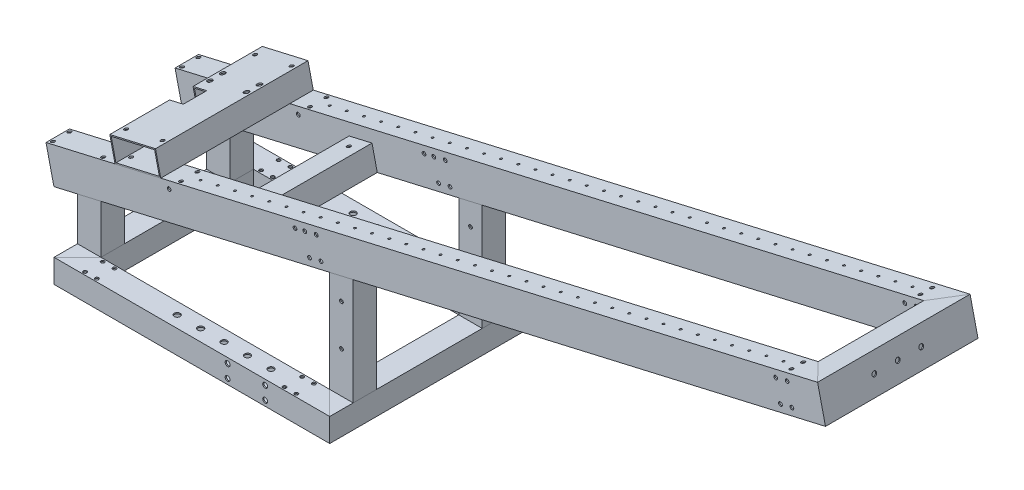
SolidWorks part; units mm, degrees
material "6061-T6 (SS)"
ref_plane "前视基准面" through (0, 0, 0) normal (0, 0, 1) x (1, 0, 0)
ref_plane "上视基准面" through (0, 0, 0) normal (0, 1, 0) x (1, 0, 0)
ref_plane "右视基准面" through (0, 0, 0) normal (1, 0, 0) x (0, 0, -1)
sketch3d "3D草图1"
  line L0 (0, 0, -212.485) -> (0, 0, 212.485) construction
  line L1 (0, 0, 75) -> (215, 0, 75)
  line L2 (215, 0, 75) -> (215, 0, -75)
  line L3 (215, 0, -75) -> (0, 0, -75)
  line L4 (0, 0, 0) -> (326.1616, 0, 0) construction
  line L5 (215, 0, 55) -> (215, 114.1, 55)
  line L6 (215, 0, -55) -> (215, 114.1, -55)
  line L7 (-33.4644, 56.7375, 55) -> (614.4917, 206.3299, 55)
  line L8 (-33.4644, 56.7375, -55) -> (614.4917, 206.3299, -55)
  line L9 (215, 114.1, 55) -> (395.6798, 114.1, 55) construction
  line L10 (0, 0, -75) -> (0, 0, 75)
  line L11 (0, 64.4633, 55) -> (0, 0, 55)
  line L12 (0, 0, 55) -> (215, 0, 55) construction
  line L13 (614.4917, 206.3299, -55) -> (614.4917, 206.3299, 55)
  line L14 (0, 0, -75) -> (0, 0, 55) construction
  line L15 (0, 64.4633, -55) -> (0, 0, -55)
  point P2 (0, 0, 0)
  point P10 (215, 0, 0)
  dimension "D3" = 55
  dimension "D1" = 215
  dimension "D2" = 150
  dimension "a" = 110
  dimension "D4" = 114.1
  dimension "D5" = 665
  dimension "h" = 255
  dimension "D8" = 13
  dimension "D6" = 255
other "方形管 20 X 20 X 2(1)"
ref_plane "基准面1" through (0, 0, -75) normal (0, 0, 1) x (1, 0, 0)
sketch "Sketch1" plane through (0, 0, -75) normal (0, 0, 1) x (1, 0, 0)
  line L0 (-9, 9) -> (-9, -9)
  line L1 (-10, 10) -> (10, 10)
  line L2 (-10, 10) -> (-10, -10)
  line L3 (-10, -10) -> (10, -10)
  line L4 (10, 10) -> (10, -10)
  line L5 (-10, 10) -> (10, -10) construction
  line L6 (-10, -10) -> (10, 10) construction
  line L7 (-9, -9) -> (9, -9)
  line L8 (9, 9) -> (9, -9)
  line L9 (-9, 9) -> (9, 9)
  point P0 (0, 0)
  dimension "D1" = 20
  dimension "D2" = 1
other "方形管 20 X 20 X 2(22)"
ref_plane "基准面3" through (-33.4644, 56.7375, 55) normal (0.9744, 0.225, 0) x (0.225, -0.9744, 0)
sketch "Sketch12" plane through (-33.4644, 56.7375, 55) normal (0.9744, 0.225, 0) x (0.225, -0.9744, 0)
  line L0 (-14, 9) -> (14, 9)
  line L1 (-15, 10) -> (15, 10)
  line L2 (-15, 10) -> (-15, -10)
  line L3 (-15, -10) -> (15, -10)
  line L4 (15, 10) -> (15, -10)
  line L5 (-15, 10) -> (15, -10) construction
  line L6 (-15, -10) -> (15, 10) construction
  line L7 (14, 9) -> (14, -9)
  line L8 (-14, -9) -> (14, -9)
  line L9 (-14, 9) -> (-14, -9)
  point P0 (0, 0)
  dimension "D1" = 20
  dimension "D2" = 30
  dimension "D3" = 1
other "剪裁/延伸4"
other "剪裁/延伸5"
sketch "草图4" plane through (638.3649, 147.3781, 0) normal (0.9744, 0.225, 0) x (0, 0, -1)
  line L0 (-65, 62.8111) -> (65, 62.8111) construction
  line L1 (-65, 77.8111) -> (-65, 47.8111) construction
  line L2 (65, 47.8111) -> (65, 77.8111) construction
  line L3 (0, 77.8111) -> (0, 47.8111) construction
  line L4 (65, 77.8111) -> (-65, 77.8111) construction
  line L5 (65, 47.8111) -> (-65, 47.8111) construction
  circle A0 centre (0, 62.8111) radius 2
  circle A1 centre (20, 62.8111) radius 2
  circle A2 centre (-20, 62.8111) radius 2
  dimension "D1" = 4
  dimension "D2" = 40
extrude "切除-拉伸1" cut sketch "草图4" against normal up to surface (20 mm away) up to face at (604.748, 204.0804, 0)
sketch "草图5" plane through (-17.5037, 75.8169, 0) normal (-0.225, 0.9744, 0) x (0.9744, 0.225, 0)
  line L0 (635.1565, -45) -> (-19.8435, -45) construction
  line L1 (-19.8435, 65) -> (655.1565, 65) construction
  line L2 (627.1565, 50) -> (627.1565, 60) construction
  line L3 (673.6837, 55) -> (-19.0857, 55) construction
  line L4 (655.1565, 65) -> (655.1565, -65) construction
  line L5 (615.1565, 55) -> (600.1565, 55) construction
  line L6 (27.1565, 48) -> (-16.8435, 48) construction
  line L7 (5.1565, 48) -> (5.1565, 75.8117) construction
  line L8 (-19.8435, 45) -> (-19.8435, 65) construction
  line L9 (0, 0) -> (900.0892, 0) construction
  line L10 (5.1565, -48) -> (5.1565, -75.8117) construction
  line L11 (27.1565, -48) -> (-16.8435, -48) construction
  line L12 (615.1565, -55) -> (600.1565, -55) construction
  line L13 (673.6837, -55) -> (-19.0857, -55) construction
  line L14 (-19.8435, 45) -> (635.1565, 45) construction
  line L15 (27.1565, 62) -> (-16.8435, 62) construction
  line L16 (-16.8435, 62) -> (-16.8435, 48) construction
  line L17 (27.1565, 62) -> (27.1565, 48) construction
  line L18 (27.1565, 55) -> (76.5565, 55) construction
  line L19 (95.1602, 62) -> (95.1602, 48) construction
  line L20 (95.1602, 55) -> (76.5565, 55) construction
  circle A1 centre (627.1565, 50) radius 1.6
  circle A3 centre (627.1565, 60) radius 1.6
  circle A6 centre (615.1565, 55) radius 1
  circle A7 centre (600.1565, 55) radius 1
  circle A8 centre (585.1565, 55) radius 1
  circle A9 centre (570.1565, 55) radius 1
  circle A10 centre (555.1565, 55) radius 1
  circle A11 centre (540.1565, 55) radius 1
  circle A12 centre (525.1565, 55) radius 1
  circle A13 centre (510.1565, 55) radius 1
  circle A14 centre (495.1565, 55) radius 1
  circle A15 centre (480.1565, 55) radius 1
  circle A16 centre (465.1565, 55) radius 1
  circle A17 centre (450.1565, 55) radius 1
  circle A18 centre (435.1565, 55) radius 1
  circle A19 centre (420.1565, 55) radius 1
  circle A20 centre (405.1565, 55) radius 1
  circle A21 centre (390.1565, 55) radius 1
  circle A22 centre (375.1565, 55) radius 1
  circle A23 centre (360.1565, 55) radius 1
  circle A24 centre (345.1565, 55) radius 1
  circle A25 centre (330.1565, 55) radius 1
  circle A26 centre (315.1565, 55) radius 1
  circle A27 centre (300.1565, 55) radius 1
  circle A28 centre (285.1565, 55) radius 1
  circle A29 centre (270.1565, 55) radius 1
  circle A30 centre (255.1565, 55) radius 1
  circle A31 centre (240.1565, 55) radius 1
  circle A32 centre (225.1565, 55) radius 1
  circle A33 centre (210.1565, 55) radius 1
  circle A34 centre (195.1565, 55) radius 1
  circle A35 centre (180.1565, 55) radius 1
  circle A36 centre (165.1565, 55) radius 1
  circle A37 centre (150.1565, 55) radius 1
  circle A38 centre (135.1565, 55) radius 1
  circle A39 centre (120.1565, 55) radius 1
  circle A40 centre (105.1565, 55) radius 1
  circle A44 centre (-16.8435, 48) radius 1.6
  circle A45 centre (27.1565, 48) radius 1.6
  circle A46 centre (44.5565, 55) radius 1.6
  circle A47 centre (76.5565, 55) radius 1.6
  circle A48 centre (95.1602, 48) radius 1.6
  circle A49 centre (-16.8435, 62) radius 1.6
  circle A50 centre (27.1565, 62) radius 1.6
  circle A51 centre (95.1602, 62) radius 1.6
  circle A52 centre (95.1602, -62) radius 1.6
  circle A53 centre (27.1565, -62) radius 1.6
  circle A54 centre (-16.8435, -62) radius 1.6
  circle A55 centre (95.1602, -48) radius 1.6
  circle A56 centre (76.5565, -55) radius 1.6
  circle A57 centre (44.5565, -55) radius 1.6
  circle A58 centre (27.1565, -48) radius 1.6
  circle A59 centre (-16.8435, -48) radius 1.6
  circle A63 centre (105.1565, -55) radius 1
  circle A64 centre (120.1565, -55) radius 1
  circle A65 centre (135.1565, -55) radius 1
  circle A66 centre (150.1565, -55) radius 1
  circle A67 centre (165.1565, -55) radius 1
  circle A68 centre (180.1565, -55) radius 1
  circle A69 centre (195.1565, -55) radius 1
  circle A70 centre (210.1565, -55) radius 1
  circle A71 centre (225.1565, -55) radius 1
  circle A72 centre (240.1565, -55) radius 1
  circle A73 centre (255.1565, -55) radius 1
  circle A74 centre (270.1565, -55) radius 1
  circle A75 centre (285.1565, -55) radius 1
  circle A76 centre (300.1565, -55) radius 1
  circle A77 centre (315.1565, -55) radius 1
  circle A78 centre (330.1565, -55) radius 1
  circle A79 centre (345.1565, -55) radius 1
  circle A80 centre (360.1565, -55) radius 1
  circle A81 centre (375.1565, -55) radius 1
  circle A82 centre (390.1565, -55) radius 1
  circle A83 centre (405.1565, -55) radius 1
  circle A84 centre (420.1565, -55) radius 1
  circle A85 centre (435.1565, -55) radius 1
  circle A86 centre (450.1565, -55) radius 1
  circle A87 centre (465.1565, -55) radius 1
  circle A88 centre (480.1565, -55) radius 1
  circle A89 centre (495.1565, -55) radius 1
  circle A90 centre (510.1565, -55) radius 1
  circle A91 centre (525.1565, -55) radius 1
  circle A92 centre (540.1565, -55) radius 1
  circle A93 centre (555.1565, -55) radius 1
  circle A94 centre (570.1565, -55) radius 1
  circle A95 centre (585.1565, -55) radius 1
  circle A96 centre (600.1565, -55) radius 1
  circle A97 centre (615.1565, -55) radius 1
  circle A100 centre (627.1565, -60) radius 1.6
  circle A102 centre (627.1565, -50) radius 1.6
  dimension "D6" = 2
  dimension "D10" = 3.2
  dimension "D3" = 3.2
  dimension "D18" = 5
  dimension "D13" = 3
  dimension "D19" = 14
  dimension "D2" = 10
  dimension "D4" = 28
  dimension "D5" = 10
  dimension "D7" = 40
  dimension "D9" = 15
  dimension "D11" = 25
  dimension "D12" = 44
  dimension "D14" = 14
  dimension "D15" = 64.4
  dimension "D16" = 32
  dimension "D17" = 532
  dimension "D8" = 35
extrude "切除-拉伸2" cut sketch "草图5" against normal up to surface (30 mm away) up to face at (293.8879, 116.9182, 55)
sketch "草图6" plane through (0, -10, 0) normal (0, -1, 0) x (1, 0, 0)
  line L0 (215, -75) -> (-27.0057, -75) construction
  line L1 (205, -65) -> (225, -85) construction
  line L3 (228.748, 0) -> (-86.5381, 0) construction
  line L4 (24, -67.5) -> (194, -67.5) construction
  line L5 (24, 67.5) -> (194, 67.5) construction
  line L6 (225, -85) -> (225, 85) construction
  circle A0 centre (24, -82.5) radius 1.5
  circle A1 centre (14, -82.5) radius 1.5
  circle A2 centre (14, -67.5) radius 1.5
  circle A3 centre (24, -67.5) radius 1.5
  circle A4 centre (194, -67.5) radius 1.5
  circle A5 centre (194, -82.5) radius 1.5
  circle A6 centre (184, -82.5) radius 1.5
  circle A7 centre (184, -67.5) radius 1.5
  circle A8 centre (184, 67.5) radius 1.5
  circle A9 centre (184, 82.5) radius 1.5
  circle A10 centre (194, 82.5) radius 1.5
  circle A11 centre (194, 67.5) radius 1.5
  circle A12 centre (24, 67.5) radius 1.5
  circle A13 centre (14, 67.5) radius 1.5
  circle A14 centre (14, 82.5) radius 1.5
  circle A15 centre (24, 82.5) radius 1.5
  dimension "D1" = 3
  dimension "D2" = 15
  dimension "D3" = 31
  dimension "D4" = 10
  dimension "D5" = 2
  dimension "D6" = 170
extrude "切除-拉伸3" cut sketch "草图6" against normal up to surface (20 mm away)
sketch "草图9" plane through (0, 0, -45) normal (0, 0, 1) x (1, 0, 0)
  line L0 (111.5664, 95.352) -> (131.0538, 99.851)
  line L1 (111.5664, 95.352) -> (116.0654, 75.8646)
  line L2 (131.0538, 99.851) -> (135.5528, 80.3636)
  line L3 (116.0654, 75.8646) -> (135.5528, 80.3636)
  line L4 (111.5664, 95.352) -> (135.5528, 80.3636) construction
  line L5 (131.0538, 99.851) -> (116.0654, 75.8646) construction
  line L6 (-30.0901, 42.1219) -> (608.1223, 189.4649) construction
  line L7 (112.7657, 94.6026) -> (130.3044, 98.6517)
  line L8 (130.3044, 98.6517) -> (134.3535, 81.113)
  line L9 (116.8148, 77.0639) -> (134.3535, 81.113)
  line L10 (112.7657, 94.6026) -> (116.8148, 77.0639)
  line L11 (-30.0901, 42.1219) -> (-36.8386, 71.353) construction
  point P1 (123.5596, 87.8578)
  dimension "D1" = 20
  dimension "D2" = 1
  dimension "D3" = 170
extrude "凸台-拉伸1" add sketch "草图9" along normal up to next (90 mm away) separate body
sketch "草图13" plane through (-17.5037, 75.8169, 0) normal (-0.225, 0.9744, 0) x (0.9744, 0.225, 0)
  line L0 (0.1565, -42) -> (20.1565, -42)
  line L1 (643.8428, 65) -> (-19.8435, 65)
  line L2 (673.2102, 71.74) -> (673.2102, -71.74)
  line L3 (643.8428, -65) -> (-19.8435, -65)
  line L4 (-19.8435, 65) -> (-19.8435, -65)
  line L6 (649.4996, 70.6569) -> (629.4996, 50.6569)
  line L7 (643.8428, 65) -> (651.6297, 72.7869)
  line L8 (660.8133, 59.3431) -> (640.8133, 39.3431)
  line L9 (673.2102, 71.74) -> (662.9434, 61.4732)
  line L10 (-19.8435, 45) -> (635.1565, 45) construction
  line L11 (655.1565, 65) -> (635.1565, 45) construction
  line L16 (635.1565, 0) -> (0, 0) construction
  line L17 (635.1565, 45) -> (635.1565, -45) construction
  line L20 (643.8428, -65) -> (651.6297, -72.7869)
  line L21 (673.2102, -71.74) -> (662.9434, -61.4732)
  line L22 (127.1565, 10) -> (127.1565, -10)
  line L23 (127.1565, 35) -> (130.1565, 35)
  line L24 (127.1565, 35) -> (127.1565, 15)
  line L25 (127.1565, 15) -> (130.1565, 15)
  line L26 (150.1565, -45) -> (150.1565, 45)
  line L27 (130.1565, -45) -> (150.1565, -45)
  line L28 (130.1565, 45) -> (130.1565, -45)
  line L29 (150.1565, 45) -> (130.1565, 45)
  line L30 (150.1565, -45) -> (150.1565, 45) construction
  line L32 (130.1565, 45) -> (130.1565, -45) construction
  line L34 (130.1565, 35) -> (130.1565, 15)
  line L35 (127.1565, 10) -> (130.1565, 10)
  line L36 (130.1565, 10) -> (130.1565, -10)
  line L37 (127.1565, -10) -> (130.1565, -10)
  line L38 (127.1565, -15) -> (127.1565, -35)
  line L39 (127.1565, -15) -> (130.1565, -15)
  line L40 (130.1565, -15) -> (130.1565, -35)
  line L41 (127.1565, -35) -> (130.1565, -35)
  line L42 (635.1565, -45) -> (-19.8435, -45) construction
  line L43 (140.1565, 45) -> (140.1565, -45) construction
  line L44 (150.1565, 45) -> (130.1565, 45) construction
  line L45 (150.1565, -45) -> (130.1565, -45) construction
  line L46 (153.1565, -15) -> (150.1565, -15)
  line L47 (150.1565, -15) -> (150.1565, -35)
  line L48 (153.1565, -35) -> (150.1565, -35)
  line L49 (153.1565, -15) -> (153.1565, -35)
  line L50 (153.1565, 10) -> (150.1565, 10)
  line L51 (150.1565, 10) -> (150.1565, -10)
  line L52 (153.1565, -10) -> (150.1565, -10)
  line L53 (153.1565, 10) -> (153.1565, -10)
  line L54 (153.1565, 15) -> (150.1565, 15)
  line L55 (150.1565, 35) -> (150.1565, 15)
  line L56 (153.1565, 35) -> (150.1565, 35)
  line L57 (153.1565, 35) -> (153.1565, 15)
  line L58 (632.1565, 10) -> (632.1565, -10)
  line L59 (632.1565, 35) -> (635.1565, 35)
  line L60 (632.1565, 35) -> (632.1565, 15)
  line L61 (632.1565, 15) -> (635.1565, 15)
  line L62 (635.1565, 35) -> (635.1565, 15)
  line L63 (632.1565, 10) -> (635.1565, 10)
  line L64 (635.1565, 10) -> (635.1565, -10)
  line L65 (632.1565, -10) -> (635.1565, -10)
  line L66 (632.1565, -15) -> (632.1565, -35)
  line L67 (632.1565, -15) -> (635.1565, -15)
  line L68 (635.1565, -15) -> (635.1565, -35)
  line L69 (632.1565, -35) -> (635.1565, -35)
  line L70 (130.1565, 37) -> (150.1565, 37)
  line L71 (130.1565, 53) -> (150.1565, 53)
  line L72 (130.1565, -53) -> (150.1565, -53)
  line L73 (130.1565, -37) -> (150.1565, -37)
  line L74 (0.1565, 47.5916) -> (130.1565, 47.5916) construction
  line L75 (-19.8435, 45) -> (0.1565, 45) construction
  line L76 (-19.8435, 45) -> (-19.8435, -45) construction
  line L77 (-19.8435, -45) -> (0.1565, -45) construction
  line L78 (0.1565, 45) -> (0.1565, -45) construction
  line L79 (65.1565, 47.5916) -> (65.1565, 105.8655) construction
  line L80 (3.1565, -15) -> (0.1565, -15)
  line L81 (0.1565, -15) -> (0.1565, -35)
  line L82 (3.1565, -35) -> (0.1565, -35)
  line L83 (3.1565, -15) -> (3.1565, -35)
  line L84 (3.1565, 10) -> (0.1565, 10)
  line L85 (0.1565, 10) -> (0.1565, -10)
  line L86 (3.1565, -10) -> (0.1565, -10)
  line L87 (3.1565, 10) -> (3.1565, -10)
  line L88 (3.1565, 15) -> (0.1565, 15)
  line L89 (0.1565, 35) -> (0.1565, 15)
  line L90 (3.1565, 35) -> (0.1565, 35)
  line L91 (3.1565, 35) -> (3.1565, 15)
  line L92 (20.1565, -45) -> (20.1565, -42)
  line L93 (0.1565, 45) -> (20.1565, 45)
  line L94 (0.1565, 45) -> (0.1565, 42)
  line L95 (0.1565, 42) -> (20.1565, 42)
  line L96 (20.1565, 45) -> (20.1565, 42)
  line L97 (0.1565, -45) -> (20.1565, -45)
  line L98 (0.1565, -45) -> (0.1565, -42)
  line L99 (66.2676, 45) -> (66.2676, 42)
  line L100 (66.2676, 45) -> (86.2676, 45)
  line L101 (86.2676, 45) -> (86.2676, 42)
  line L102 (66.2676, 42) -> (86.2676, 42)
  line L103 (66.2676, -42) -> (86.2676, -42)
  line L104 (86.2676, -45) -> (86.2676, -42)
  line L105 (66.2676, -45) -> (86.2676, -45)
  line L106 (66.2676, -45) -> (66.2676, -42)
  line L115 (198.4898, 45) -> (198.4898, 42)
  line L116 (198.4898, 45) -> (218.4898, 45)
  line L117 (218.4898, 45) -> (218.4898, 42)
  line L118 (198.4898, 42) -> (218.4898, 42)
  line L119 (198.4898, -42) -> (218.4898, -42)
  line L120 (218.4898, -45) -> (218.4898, -42)
  line L121 (198.4898, -45) -> (218.4898, -45)
  line L122 (198.4898, -45) -> (198.4898, -42)
  line L123 (264.6009, 45) -> (264.6009, 42)
  line L124 (264.6009, 45) -> (284.6009, 45)
  line L125 (284.6009, 45) -> (284.6009, 42)
  line L126 (264.6009, 42) -> (284.6009, 42)
  line L127 (264.6009, -42) -> (284.6009, -42)
  line L128 (284.6009, -45) -> (284.6009, -42)
  line L129 (264.6009, -45) -> (284.6009, -45)
  line L130 (264.6009, -45) -> (264.6009, -42)
  line L131 (330.712, 45) -> (330.712, 42)
  line L132 (330.712, 45) -> (350.712, 45)
  line L133 (350.712, 45) -> (350.712, 42)
  line L134 (330.712, 42) -> (350.712, 42)
  line L135 (330.712, -42) -> (350.712, -42)
  line L136 (350.712, -45) -> (350.712, -42)
  line L137 (330.712, -45) -> (350.712, -45)
  line L138 (330.712, -45) -> (330.712, -42)
  line L139 (396.8231, 45) -> (396.8231, 42)
  line L140 (396.8231, 45) -> (416.8231, 45)
  line L141 (416.8231, 45) -> (416.8231, 42)
  line L142 (396.8231, 42) -> (416.8231, 42)
  line L143 (396.8231, -42) -> (416.8231, -42)
  line L144 (416.8231, -45) -> (416.8231, -42)
  line L145 (396.8231, -45) -> (416.8231, -45)
  line L146 (396.8231, -45) -> (396.8231, -42)
  line L147 (462.9343, 45) -> (462.9343, 42)
  line L148 (462.9343, 45) -> (482.9343, 45)
  line L149 (482.9343, 45) -> (482.9343, 42)
  line L150 (462.9343, 42) -> (482.9343, 42)
  line L151 (462.9343, -42) -> (482.9343, -42)
  line L152 (482.9343, -45) -> (482.9343, -42)
  line L153 (462.9343, -45) -> (482.9343, -45)
  line L154 (462.9343, -45) -> (462.9343, -42)
  line L155 (529.0454, 45) -> (529.0454, 42)
  line L156 (529.0454, 45) -> (549.0454, 45)
  line L157 (549.0454, 45) -> (549.0454, 42)
  line L158 (529.0454, 42) -> (549.0454, 42)
  line L159 (529.0454, -42) -> (549.0454, -42)
  line L160 (549.0454, -45) -> (549.0454, -42)
  line L161 (529.0454, -45) -> (549.0454, -45)
  line L162 (529.0454, -45) -> (529.0454, -42)
  line L163 (595.1565, 45) -> (595.1565, 42)
  line L164 (595.1565, 45) -> (615.1565, 45)
  line L165 (615.1565, 45) -> (615.1565, 42)
  line L166 (595.1565, 42) -> (615.1565, 42)
  line L167 (595.1565, -42) -> (615.1565, -42)
  line L168 (615.1565, -45) -> (615.1565, -42)
  line L169 (595.1565, -45) -> (615.1565, -45)
  line L170 (595.1565, -45) -> (595.1565, -42)
  line L171 (132.3787, 45) -> (132.3787, 42) [skipped]
  line L172 (132.3787, 42) -> (152.3787, 42) [skipped]
  line L173 (152.3787, 45) -> (152.3787, 42) [skipped]
  line L174 (132.3787, 45) -> (152.3787, 45) [skipped]
  line L175 (132.3787, -42) -> (152.3787, -42) [skipped]
  line L176 (152.3787, -45) -> (152.3787, -42) [skipped]
  line L177 (132.3787, -45) -> (152.3787, -45) [skipped]
  line L178 (132.3787, -45) -> (132.3787, -42) [skipped]
  line L179 (651.6297, 72.7869) -> (656.4558, 45)
  line L180 (635.1565, 45) -> (655.1565, 65) construction
  line L181 (662.9434, 61.4732) -> (635.1565, 66.2993)
  line L182 (656.4558, 45) -> (635.1565, 66.2993)
  line L183 (662.9434, -61.4732) -> (635.1565, -66.2993)
  line L184 (656.4558, -45) -> (635.1565, -66.2993)
  line L185 (651.6297, -72.7869) -> (656.4558, -45)
  arc A2 (130.1565, 53) -> (130.1565, 37) centre (130.1565, 45) ccw
  circle A3 centre (95.1602, 62) radius 1.6
  circle A4 centre (95.1602, 62) radius 1.6
  circle A5 centre (27.1565, 62) radius 1.6
  circle A6 centre (27.1565, 62) radius 1.6
  circle A7 centre (-16.8435, 62) radius 1.6
  circle A8 centre (-16.8435, 62) radius 1.6
  circle A9 centre (95.1602, 48) radius 1.6
  circle A10 centre (95.1602, 48) radius 1.6
  circle A11 centre (76.5565, 55) radius 1.6
  circle A12 centre (76.5565, 55) radius 1.6
  circle A13 centre (44.5565, 55) radius 1.6
  circle A14 centre (44.5565, 55) radius 1.6
  circle A15 centre (27.1565, 48) radius 1.6
  circle A16 centre (27.1565, 48) radius 1.6
  circle A17 centre (-16.8435, 48) radius 1.6
  circle A18 centre (-16.8435, 48) radius 1.6
  circle A19 centre (105.1565, 55) radius 1
  circle A20 centre (105.1565, 55) radius 1
  circle A21 centre (120.1565, 55) radius 1
  circle A22 centre (120.1565, 55) radius 1
  circle A23 centre (135.1565, 55) radius 1
  circle A24 centre (135.1565, 55) radius 1
  circle A25 centre (150.1565, 55) radius 1
  circle A26 centre (150.1565, 55) radius 1
  circle A27 centre (165.1565, 55) radius 1
  circle A28 centre (165.1565, 55) radius 1
  circle A29 centre (180.1565, 55) radius 1
  circle A30 centre (180.1565, 55) radius 1
  circle A31 centre (195.1565, 55) radius 1
  circle A32 centre (195.1565, 55) radius 1
  circle A33 centre (210.1565, 55) radius 1
  circle A34 centre (210.1565, 55) radius 1
  circle A35 centre (225.1565, 55) radius 1
  circle A36 centre (225.1565, 55) radius 1
  circle A37 centre (240.1565, 55) radius 1
  circle A38 centre (240.1565, 55) radius 1
  circle A39 centre (255.1565, 55) radius 1
  circle A40 centre (255.1565, 55) radius 1
  circle A41 centre (270.1565, 55) radius 1
  circle A42 centre (270.1565, 55) radius 1
  circle A43 centre (285.1565, 55) radius 1
  circle A44 centre (285.1565, 55) radius 1
  circle A45 centre (300.1565, 55) radius 1
  circle A46 centre (300.1565, 55) radius 1
  circle A47 centre (315.1565, 55) radius 1
  circle A48 centre (315.1565, 55) radius 1
  circle A49 centre (330.1565, 55) radius 1
  circle A50 centre (330.1565, 55) radius 1
  circle A51 centre (345.1565, 55) radius 1
  circle A52 centre (345.1565, 55) radius 1
  circle A53 centre (360.1565, 55) radius 1
  circle A54 centre (360.1565, 55) radius 1
  circle A55 centre (375.1565, 55) radius 1
  circle A56 centre (375.1565, 55) radius 1
  circle A57 centre (390.1565, 55) radius 1
  circle A58 centre (390.1565, 55) radius 1
  circle A59 centre (405.1565, 55) radius 1
  circle A60 centre (405.1565, 55) radius 1
  circle A61 centre (420.1565, 55) radius 1
  circle A62 centre (420.1565, 55) radius 1
  circle A63 centre (435.1565, 55) radius 1
  circle A64 centre (435.1565, 55) radius 1
  circle A65 centre (450.1565, 55) radius 1
  circle A66 centre (450.1565, 55) radius 1
  circle A67 centre (465.1565, 55) radius 1
  circle A68 centre (465.1565, 55) radius 1
  circle A69 centre (480.1565, 55) radius 1
  circle A70 centre (480.1565, 55) radius 1
  circle A71 centre (495.1565, 55) radius 1
  circle A72 centre (495.1565, 55) radius 1
  circle A73 centre (510.1565, 55) radius 1
  circle A74 centre (510.1565, 55) radius 1
  circle A75 centre (525.1565, 55) radius 1
  circle A76 centre (525.1565, 55) radius 1
  circle A77 centre (540.1565, 55) radius 1
  circle A78 centre (540.1565, 55) radius 1
  circle A79 centre (555.1565, 55) radius 1
  circle A80 centre (555.1565, 55) radius 1
  circle A81 centre (570.1565, 55) radius 1
  circle A82 centre (570.1565, 55) radius 1
  circle A83 centre (585.1565, 55) radius 1
  circle A84 centre (585.1565, 55) radius 1
  circle A85 centre (600.1565, 55) radius 1
  circle A86 centre (600.1565, 55) radius 1
  circle A87 centre (615.1565, 55) radius 1
  circle A88 centre (615.1565, 55) radius 1
  circle A89 centre (627.1565, 60) radius 1.6
  circle A90 centre (627.1565, 60) radius 1.6
  circle A91 centre (627.1565, 50) radius 1.6
  circle A92 centre (627.1565, 50) radius 1.6
  circle A93 centre (627.1565, -50) radius 1.6
  circle A94 centre (627.1565, -50) radius 1.6
  circle A95 centre (627.1565, -60) radius 1.6
  circle A96 centre (627.1565, -60) radius 1.6
  circle A97 centre (615.1565, -55) radius 1
  circle A98 centre (615.1565, -55) radius 1
  circle A99 centre (600.1565, -55) radius 1
  circle A100 centre (600.1565, -55) radius 1
  circle A101 centre (585.1565, -55) radius 1
  circle A102 centre (585.1565, -55) radius 1
  circle A103 centre (570.1565, -55) radius 1
  circle A104 centre (570.1565, -55) radius 1
  circle A105 centre (555.1565, -55) radius 1
  circle A106 centre (555.1565, -55) radius 1
  circle A107 centre (540.1565, -55) radius 1
  circle A108 centre (540.1565, -55) radius 1
  circle A109 centre (525.1565, -55) radius 1
  circle A110 centre (525.1565, -55) radius 1
  circle A111 centre (510.1565, -55) radius 1
  circle A112 centre (510.1565, -55) radius 1
  circle A113 centre (495.1565, -55) radius 1
  circle A114 centre (495.1565, -55) radius 1
  circle A115 centre (480.1565, -55) radius 1
  circle A116 centre (480.1565, -55) radius 1
  circle A117 centre (465.1565, -55) radius 1
  circle A118 centre (465.1565, -55) radius 1
  circle A119 centre (450.1565, -55) radius 1
  circle A120 centre (450.1565, -55) radius 1
  circle A121 centre (435.1565, -55) radius 1
  circle A122 centre (435.1565, -55) radius 1
  circle A123 centre (420.1565, -55) radius 1
  circle A124 centre (420.1565, -55) radius 1
  circle A125 centre (405.1565, -55) radius 1
  circle A126 centre (405.1565, -55) radius 1
  circle A127 centre (390.1565, -55) radius 1
  circle A128 centre (390.1565, -55) radius 1
  circle A129 centre (375.1565, -55) radius 1
  circle A130 centre (375.1565, -55) radius 1
  circle A131 centre (360.1565, -55) radius 1
  circle A132 centre (360.1565, -55) radius 1
  circle A133 centre (345.1565, -55) radius 1
  circle A134 centre (345.1565, -55) radius 1
  circle A135 centre (330.1565, -55) radius 1
  circle A136 centre (330.1565, -55) radius 1
  circle A137 centre (315.1565, -55) radius 1
  circle A138 centre (315.1565, -55) radius 1
  circle A139 centre (300.1565, -55) radius 1
  circle A140 centre (300.1565, -55) radius 1
  circle A141 centre (285.1565, -55) radius 1
  circle A142 centre (285.1565, -55) radius 1
  circle A143 centre (270.1565, -55) radius 1
  circle A144 centre (270.1565, -55) radius 1
  circle A145 centre (255.1565, -55) radius 1
  circle A146 centre (255.1565, -55) radius 1
  circle A147 centre (240.1565, -55) radius 1
  circle A148 centre (240.1565, -55) radius 1
  circle A149 centre (225.1565, -55) radius 1
  circle A150 centre (225.1565, -55) radius 1
  circle A151 centre (210.1565, -55) radius 1
  circle A152 centre (210.1565, -55) radius 1
  circle A153 centre (195.1565, -55) radius 1
  circle A154 centre (195.1565, -55) radius 1
  circle A155 centre (180.1565, -55) radius 1
  circle A156 centre (180.1565, -55) radius 1
  circle A157 centre (165.1565, -55) radius 1
  circle A158 centre (165.1565, -55) radius 1
  circle A159 centre (150.1565, -55) radius 1
  circle A160 centre (150.1565, -55) radius 1
  circle A161 centre (135.1565, -55) radius 1
  circle A162 centre (135.1565, -55) radius 1
  circle A163 centre (120.1565, -55) radius 1
  circle A164 centre (120.1565, -55) radius 1
  circle A165 centre (105.1565, -55) radius 1
  circle A166 centre (105.1565, -55) radius 1
  circle A167 centre (-16.8435, -48) radius 1.6
  circle A168 centre (-16.8435, -48) radius 1.6
  circle A169 centre (27.1565, -48) radius 1.6
  circle A170 centre (27.1565, -48) radius 1.6
  circle A171 centre (44.5565, -55) radius 1.6
  circle A172 centre (44.5565, -55) radius 1.6
  circle A173 centre (76.5565, -55) radius 1.6
  circle A174 centre (76.5565, -55) radius 1.6
  circle A175 centre (95.1602, -48) radius 1.6
  circle A176 centre (95.1602, -48) radius 1.6
  circle A177 centre (-16.8435, -62) radius 1.6
  circle A178 centre (-16.8435, -62) radius 1.6
  circle A179 centre (27.1565, -62) radius 1.6
  circle A180 centre (27.1565, -62) radius 1.6
  circle A181 centre (95.1602, -62) radius 1.6
  circle A182 centre (95.1602, -62) radius 1.6
  arc A183 (150.1565, 37) -> (150.1565, 53) centre (150.1565, 45) ccw
  arc A184 (150.1565, -37) -> (150.1565, -53) centre (150.1565, -45) cw
  arc A185 (130.1565, -53) -> (130.1565, -37) centre (130.1565, -45) cw
  dimension "D104" = 16
  dimension "D94" = 3
  dimension "D95" = 20
  dimension "D97" = 10
  dimension "D98" = 10
  dimension "D99" = 20
  dimension "D100" = 10
  dimension "D101" = 3
  dimension "D103" = 10
  dimension "D105" = 10
  dimension "D106" = 3
  dimension "D107" = 20
  dimension "D108" = 20
  dimension "D109" = 20
  dimension "D1" = 8
  dimension "D2" = 8
  dimension "D3" = 0
  dimension "D4" = 0
  dimension "D5" = 0
  dimension "D6" = 0
  dimension "D7" = 0
  dimension "D8" = 0
  dimension "D9" = 0
  dimension "D10" = 0
  dimension "D11" = 0
  dimension "D12" = 0
  dimension "D13" = 0
  dimension "D14" = 0
  dimension "D15" = 0
  dimension "D16" = 0
  dimension "D17" = 0
  dimension "D18" = 0
  dimension "D19" = 0
  dimension "D20" = 0
  dimension "D21" = 0
  dimension "D22" = 0
  dimension "D23" = 0
  dimension "D24" = 0
  dimension "D25" = 0
  dimension "D26" = 0
  dimension "D27" = 0
  dimension "D28" = 0
  dimension "D29" = 0
  dimension "D30" = 0
  dimension "D31" = 0
  dimension "D32" = 0
  dimension "D33" = 0
  dimension "D34" = 0
  dimension "D35" = 0
  dimension "D36" = 0
  dimension "D37" = 0
  dimension "D38" = 0
  dimension "D39" = 0
  dimension "D40" = 0
  dimension "D41" = 0
  dimension "D42" = 0
  dimension "D43" = 0
  dimension "D44" = 0
  dimension "D45" = 0
  dimension "D46" = 0
  dimension "D47" = 0
  dimension "D48" = 0
  dimension "D49" = 0
  dimension "D50" = 0
  dimension "D51" = 0
  dimension "D52" = 0
  dimension "D53" = 0
  dimension "D54" = 0
  dimension "D55" = 0
  dimension "D56" = 0
  dimension "D57" = 0
  dimension "D58" = 0
  dimension "D59" = 0
  dimension "D60" = 0
  dimension "D61" = 0
  dimension "D62" = 0
  dimension "D63" = 0
  dimension "D64" = 0
  dimension "D65" = 0
  dimension "D66" = 0
  dimension "D67" = 0
  dimension "D68" = 0
  dimension "D69" = 0
  dimension "D70" = 0
  dimension "D71" = 0
  dimension "D72" = 0
  dimension "D73" = 0
  dimension "D74" = 0
  dimension "D75" = 0
  dimension "D76" = 0
  dimension "D77" = 0
  dimension "D78" = 0
  dimension "D79" = 0
  dimension "D80" = 0
  dimension "D81" = 0
  dimension "D82" = 0
  dimension "D83" = 0
  dimension "D84" = 0
  dimension "D85" = 0
  dimension "D86" = 0
  dimension "D87" = 0
  dimension "D88" = 0
  dimension "D89" = 0
  dimension "D90" = 0
  dimension "D91" = 0
  dimension "D92" = 0
  dimension "D93" = 0
  dimension "D96" = 3
  dimension "D102" = 3
extrude "凸台-拉伸2" [suppressed] add sketch "草图13" along normal blind 2 separate body
sketch "草图15" plane through (0, 0, 65) normal (0, 0, 1) x (1, 0, 0)
  line L0 (624.2354, 208.5794) -> (596.9531, 202.2808) construction
  line L1 (627.6097, 193.9639) -> (620.8612, 223.195) construction
  line L2 (620.8612, 223.195) -> (-36.8386, 71.353) construction
  line L3 (596.9531, 202.2808) -> (593.5788, 216.8964) construction
  line L4 (596.9531, 202.2808) -> (592.0812, 201.1561) construction
  line L5 (592.0812, 201.1561) -> (588.7069, 215.7716) construction
  line L6 (-33.4644, 56.7375) -> (297.7909, 133.2138) construction
  line L7 (-36.8386, 71.353) -> (-30.0901, 42.1219) construction
  line L8 (183.7443, 116.1208) -> (193.488, 118.3703) construction
  line L9 (183.7443, 116.1208) -> (187.7935, 98.5821) construction
  circle A0 centre (594.9285, 211.0501) radius 1.6
  circle A1 centre (598.9776, 193.5115) radius 1.6
  circle A2 centre (589.2339, 191.262) radius 1.6
  circle A3 centre (585.1848, 208.8006) radius 1.6
  circle A8 centre (183.7443, 116.1208) radius 1.6
  circle A9 centre (193.488, 118.3703) radius 1.6
  circle A10 centre (197.5372, 100.8316) radius 1.6
  circle A11 centre (187.7935, 98.5821) radius 1.6
  dimension "D2" = 3.2
  dimension "D3" = 18
  dimension "D6" = 18
  dimension "D5" = 10
  dimension "D7" = 225
  dimension "D8" = 3.2
  dimension "D1" = 28
  dimension "D4" = 5
extrude "切除-拉伸9" cut sketch "草图15" against normal through all
sketch "草图16" plane through (-17.5037, 75.8169, 0) normal (-0.225, 0.9744, 0) x (0.9744, 0.225, 0)
  line L0 (76.5565, 55) -> (44.5565, 55) construction
  line L1 (60.5565, 55) -> (60.5565, -65.8368) construction
  line L2 (0, 0) -> (132.2176, 0) construction
  line L3 (655.1565, -65) -> (-19.8435, -65) construction
  line L4 (80.5565, 65) -> (40.5565, 65)
  line L5 (80.5565, 65) -> (80.5565, -65)
  line L6 (80.5565, -65) -> (40.5565, -65)
  line L7 (40.5565, 65) -> (40.5565, -65)
  line L8 (80.5565, 65) -> (40.5565, -65) construction
  line L9 (80.5565, -65) -> (40.5565, 65) construction
  line L11 (52.5565, -14) -> (40.5565, -14)
  line L12 (52.5565, -14) -> (52.5565, 6)
  line L13 (52.5565, 6) -> (40.5565, 6)
  line L14 (40.5565, -14) -> (40.5565, 6)
  line L15 (52.5565, -14) -> (40.5565, 6) construction
  line L16 (52.5565, 6) -> (40.5565, -14) construction
  circle A0 centre (76.5565, 55) radius 1.6 construction
  circle A1 centre (76.5565, 55) radius 1.6
  circle A2 centre (44.5565, 55) radius 1.6 construction
  circle A3 centre (44.5565, 55) radius 1.6
  circle A4 centre (76.5565, -55) radius 1.6 construction
  circle A5 centre (76.5565, -55) radius 1.6
  circle A6 centre (44.5565, -55) radius 1.6 construction
  circle A7 centre (44.5565, -55) radius 1.6
  point P9 (60.5565, 0)
  point P27 (46.5565, -4)
  dimension "D1" = 40
  dimension "D2" = 12
  dimension "D3" = 20
  dimension "D4" = 51
extrude "凸台-拉伸5" add sketch "草图16" along normal blind 20 separate body
sketch "草图17" plane through (0, 0, -65) normal (0, 0, -1) x (-1, 0, 0)
  line L0 (-59.7888, 94.6875) -> (-22.7627, 86.1394)
  line L1 (-22.7627, 86.1394) -> (-18.7136, 103.6781)
  line L2 (-18.7136, 103.6781) -> (-55.7397, 112.2262)
  line L3 (-55.7397, 112.2262) -> (-59.7888, 94.6875)
  line L4 (-60.9881, 93.9381) -> (-22.0133, 84.9401)
  line L5 (-22.0133, 84.9401) -> (-17.5143, 104.4275)
  line L6 (-60.9881, 93.9381) -> (-22.0133, 84.9401)
  line L7 (-56.4891, 113.4255) -> (-60.9881, 93.9381)
  line L9 (-22.0133, 84.9401) -> (-17.5143, 104.4275)
  line L11 (-56.4891, 113.4255) -> (-60.9881, 93.9381)
  line L16 (-60.9881, 93.9381) -> (-22.0133, 84.9401) construction
  line L17 (-17.5143, 104.4275) -> (-56.4891, 113.4255) construction
  line L18 (-17.5143, 104.4275) -> (-56.4891, 113.4255)
  line L19 (-17.5143, 104.4275) -> (-56.4891, 113.4255)
  dimension "D1" = 0
  dimension "D2" = 1
extrude "切除-拉伸10" cut sketch "草图17" against normal through all contours L2 L3 L0 L1
sketch "草图19" plane through (-15.2542, 66.0732, 0) normal (-0.225, 0.9744, 0) x (0.9744, 0.225, 0)
  line L0 (140.1565, 45) -> (140.1565, -45) construction
  line L1 (150.1565, 45) -> (130.1565, 45) construction
  line L2 (150.1565, -45) -> (130.1565, -45) construction
  line L3 (140.1565, 0) -> (147.6997, 0) construction
  circle A0 centre (140.1565, 35) radius 1.6
  circle A1 centre (140.1565, -35) radius 1.6
  dimension "D1" = 3.2
  dimension "D2" = 70
extrude "切除-拉伸11" cut sketch "草图19" against normal through all
sketch "草图21" plane through (0, 0, -85) normal (0, 0, -1) x (-1, 0, 0)
  line L0 (-225, 0) -> (-119.1159, 0) construction
  line L1 (-225, -10) -> (-225, 10) construction
  line L2 (-225, 10) -> (-225, -10) construction
  circle A0 centre (-170, -5.5) radius 2.1
  circle A1 centre (-138, -5.5) radius 2.1
  circle A2 centre (-138, 5.5) radius 2.1
  circle A3 centre (-170, 5.5) radius 2.1
  dimension "D1" = 32
  dimension "D3" = 4.2
  dimension "D2" = 11
  dimension "D4" = 55
extrude "切除-拉伸16" cut sketch "草图21" against normal through all
sketch "草图22" plane through (0, 0, 65) normal (0, 0, 1) x (1, 0, 0)
  line L0 (-33.4644, 56.7375) -> (624.2354, 208.5794) construction
  line L1 (-36.8386, 71.353) -> (-30.0901, 42.1219) construction
  line L2 (620.8612, 223.195) -> (627.6097, 193.9639) construction
  line L3 (56.4891, 113.4255) -> (60.9881, 93.9381) construction
  line L4 (68.184, 89.4416) -> (175.3648, 114.1862) construction
  circle A0 centre (68.184, 89.4416) radius 1.6
  circle A1 centre (175.3648, 114.1862) radius 1.6
  dimension "D1" = 3.2
  dimension "D3" = 9
  dimension "D2" = 6
  dimension "D4" = 110
extrude "切除-拉伸17" cut sketch "草图22" against normal through all
sketch "草图23" plane through (0, -10, 0) normal (0, -1, 0) x (1, 0, 0)
  line L0 (225, 0) -> (-10, 0) construction
  line L1 (225, -85) -> (225, 85) construction
  line L2 (-10, 85) -> (-10, -85) construction
  line L3 (215, 75) -> (0, 75) construction
  line L4 (205, 65) -> (225, 85) construction
  line L5 (10, 65) -> (-10, 85) construction
  line L6 (165, 75) -> (145, 75) construction
  circle A0 centre (165, 75) radius 2.5
  circle A1 centre (145, 75) radius 2.5
  circle A2 centre (125, 75) radius 2.5
  circle A3 centre (105, 75) radius 2.5
  circle A4 centre (85, 75) radius 2.5
  circle A5 centre (85, -75) radius 2.5
  circle A6 centre (105, -75) radius 2.5
  circle A7 centre (125, -75) radius 2.5
  circle A8 centre (145, -75) radius 2.5
  circle A9 centre (165, -75) radius 2.5
  dimension "D1" = 5
  dimension "D4" = 5
  dimension "D2" = 20
  dimension "D3" = 60
extrude "切除-拉伸18" cut sketch "草图23" against normal up to surface (20 mm away)
sketch "草图25" plane through (0, -10, 0) normal (0, -1, 0) x (1, 0, 0)
  line L0 (197.5, 85) -> (197.5, 65)
  line L1 (225, 85) -> (-10, 85) construction
  line L2 (205, 65) -> (10, 65) construction
  line L3 (205, 50) -> (205, 0)
  line L4 (205, -65) -> (205, 65) construction
  line L5 (247.8115, 0) -> (0, 0) construction
  line L6 (205, 50) -> (225, 50)
  line L7 (225, -85) -> (225, 85) construction
  line L8 (11, 85) -> (11, 65)
  line L9 (10, 50) -> (-10, 50)
  line L10 (10, 65) -> (10, -65) construction
  line L11 (-10, 85) -> (-10, -85) construction
  line L12 (197.5, 85) -> (11, 85)
  line L13 (-10, 50) -> (-10, -50)
  line L14 (225, 50) -> (225, -50)
  line L15 (201, -5) -> (205, -5)
  line L16 (201, 39) -> (205, 39)
  line L17 (201, 39) -> (201, 27)
  line L18 (201, 27) -> (205, 27)
  line L19 (205, 39) -> (205, 27)
  line L20 (201, 39) -> (205, 27) construction
  line L21 (201, 27) -> (205, 39) construction
  line L22 (201, 17) -> (205, 17)
  line L23 (201, 17) -> (201, 5)
  line L24 (201, 5) -> (205, 5)
  line L25 (205, 17) -> (205, 5)
  line L26 (201, 17) -> (205, 5) construction
  line L27 (201, 5) -> (205, 17) construction
  line L28 (205, -17) -> (205, -5)
  line L29 (201, -17) -> (205, -17)
  line L30 (201, -17) -> (201, -5)
  line L31 (201, -27) -> (205, -27)
  line L32 (205, -39) -> (205, -27)
  line L33 (201, -39) -> (205, -39)
  line L34 (201, -39) -> (201, -27)
  line L35 (14, 17) -> (14, 5)
  line L36 (14, 39) -> (10, 39)
  line L37 (14, 39) -> (14, 27)
  line L38 (14, 27) -> (10, 27)
  line L39 (10, 39) -> (10, 27)
  line L40 (14, 39) -> (10, 27) construction
  line L41 (14, 27) -> (10, 39) construction
  line L42 (14, 17) -> (10, 17)
  line L43 (10, 17) -> (10, 5)
  line L44 (14, 5) -> (10, 5)
  line L45 (14, -5) -> (14, -17)
  line L46 (14, -5) -> (10, -5)
  line L47 (10, -5) -> (10, -17)
  line L48 (14, -17) -> (10, -17)
  line L49 (14, -27) -> (14, -39)
  line L50 (14, -27) -> (10, -27)
  line L51 (10, -27) -> (10, -39)
  line L52 (14, -39) -> (10, -39)
  line L53 (130, 61) -> (130, 65)
  line L54 (175, 61) -> (163, 61)
  line L55 (175, 61) -> (175, 65)
  line L56 (175, 65) -> (163, 65)
  line L57 (163, 61) -> (163, 65)
  line L58 (175, 61) -> (163, 65) construction
  line L59 (175, 65) -> (163, 61) construction
  line L60 (130, 61) -> (118, 61)
  line L61 (118, 61) -> (118, 65)
  line L62 (130, 65) -> (118, 65)
  line L63 (85, 61) -> (85, 65)
  line L64 (85, 61) -> (73, 61)
  line L65 (73, 61) -> (73, 65)
  line L66 (85, 65) -> (73, 65)
  line L67 (40, 61) -> (40, 65)
  line L68 (40, 61) -> (28, 61)
  line L69 (28, 61) -> (28, 65)
  line L70 (40, 65) -> (28, 65)
  line L71 (175, 61) -> (130, 61) construction
  line L72 (40, -61) -> (28, -61)
  line L73 (28, -61) -> (28, -65)
  line L74 (40, -65) -> (28, -65)
  line L75 (40, -61) -> (40, -65)
  line L76 (85, -61) -> (73, -61)
  line L77 (73, -61) -> (73, -65)
  line L78 (85, -65) -> (73, -65)
  line L79 (85, -61) -> (85, -65)
  line L80 (130, -61) -> (118, -61)
  line L81 (118, -61) -> (118, -65)
  line L82 (130, -65) -> (118, -65)
  line L83 (130, -61) -> (130, -65)
  line L84 (175, -65) -> (163, -65)
  line L85 (163, -61) -> (163, -65)
  line L86 (175, -61) -> (163, -61)
  line L87 (175, -61) -> (175, -65)
  line L88 (10, -50) -> (-10, -50)
  line L89 (11, -85) -> (11, -65)
  line L90 (197.5, -85) -> (11, -85)
  line L91 (197.5, -85) -> (197.5, -65)
  line L92 (205, -50) -> (225, -50)
  arc A0 (197.5, 65) -> (205, 50) centre (197.5, 55.625) ccw
  circle A1 centre (194, -67.5) radius 1.5
  circle A2 centre (194, -67.5) radius 1.5
  circle A3 centre (184, -67.5) radius 1.5
  circle A4 centre (184, -67.5) radius 1.5
  circle A5 centre (184, -82.5) radius 1.5
  circle A6 centre (184, -82.5) radius 1.5
  circle A7 centre (194, -82.5) radius 1.5
  circle A8 centre (194, -82.5) radius 1.5
  circle A9 centre (24, -67.5) radius 1.5
  circle A10 centre (24, -67.5) radius 1.5
  circle A11 centre (14, -67.5) radius 1.5
  circle A12 centre (14, -67.5) radius 1.5
  circle A13 centre (14, -82.5) radius 1.5
  circle A14 centre (14, -82.5) radius 1.5
  circle A15 centre (24, -82.5) radius 1.5
  circle A16 centre (24, -82.5) radius 1.5
  circle A17 centre (165, -75) radius 2.5
  circle A18 centre (165, -75) radius 2.5
  circle A19 centre (145, -75) radius 2.5
  circle A20 centre (145, -75) radius 2.5
  circle A21 centre (125, -75) radius 2.5
  circle A22 centre (125, -75) radius 2.5
  circle A23 centre (105, -75) radius 2.5
  circle A24 centre (105, -75) radius 2.5
  circle A25 centre (85, -75) radius 2.5
  circle A26 centre (85, -75) radius 2.5
  circle A27 centre (24, 82.5) radius 1.5
  circle A28 centre (24, 82.5) radius 1.5
  circle A29 centre (14, 82.5) radius 1.5
  circle A30 centre (14, 82.5) radius 1.5
  circle A31 centre (14, 67.5) radius 1.5
  circle A32 centre (14, 67.5) radius 1.5
  circle A33 centre (24, 67.5) radius 1.5
  circle A34 centre (24, 67.5) radius 1.5
  circle A35 centre (194, 67.5) radius 1.5
  circle A36 centre (194, 67.5) radius 1.5
  circle A37 centre (194, 82.5) radius 1.5
  circle A38 centre (194, 82.5) radius 1.5
  circle A39 centre (184, 82.5) radius 1.5
  circle A40 centre (184, 82.5) radius 1.5
  circle A41 centre (184, 67.5) radius 1.5
  circle A42 centre (184, 67.5) radius 1.5
  circle A43 centre (85, 75) radius 2.5
  circle A44 centre (85, 75) radius 2.5
  circle A45 centre (105, 75) radius 2.5
  circle A46 centre (105, 75) radius 2.5
  circle A47 centre (125, 75) radius 2.5
  circle A48 centre (125, 75) radius 2.5
  circle A49 centre (145, 75) radius 2.5
  circle A50 centre (145, 75) radius 2.5
  circle A51 centre (165, 75) radius 2.5
  circle A52 centre (165, 75) radius 2.5
  arc A53 (11, 65) -> (10, 50) centre (11, 57.4667) cw
  arc A54 (11, -65) -> (10, -50) centre (11, -57.4667) ccw
  arc A55 (197.5, -65) -> (205, -50) centre (197.5, -55.625) cw
  point P105 (203, 33)
  point P112 (203, 11)
  point P125 (203, 17)
  point P126 (12, 33)
  point P131 (169, 63)
  point P179 (-10, 0)
  point P188 (225, 0)
  dimension "D29" = 3
  dimension "D30" = 4
  dimension "D27" = 3.5
  dimension "D28" = 15
  dimension "D31" = 12
  dimension "D32" = 10
  dimension "D33" = 22
  dimension "D34" = 4
  dimension "D35" = 12
  dimension "D37" = 10
  dimension "D38" = 4
  dimension "D39" = 12
  dimension "D40" = 30
  dimension "D42" = 45
  dimension "D1" = 0
  dimension "D2" = 0
  dimension "D3" = 0
  dimension "D4" = 0
  dimension "D5" = 0
  dimension "D6" = 0
  dimension "D7" = 0
  dimension "D8" = 0
  dimension "D9" = 0
  dimension "D10" = 0
  dimension "D11" = 0
  dimension "D12" = 0
  dimension "D13" = 0
  dimension "D14" = 0
  dimension "D15" = 0
  dimension "D16" = 0
  dimension "D17" = 0
  dimension "D18" = 0
  dimension "D19" = 0
  dimension "D20" = 0
  dimension "D21" = 0
  dimension "D22" = 0
  dimension "D23" = 0
  dimension "D24" = 0
  dimension "D25" = 0
  dimension "D26" = 0
  dimension "D36" = 4
  dimension "D41" = 4
extrude "凸台-拉伸6" [suppressed] add sketch "草图25" along normal blind 2 separate body
fillet "圆角1" [suppressed] radius 3
sketch "草图26" plane through (-22.0027, 95.3043, 0) normal (-0.225, 0.9744, 0) x (0.9744, 0.225, 0)
  line L0 (60.5565, 65) -> (60.5565, -65) construction
  line L1 (80.5565, 65) -> (40.5565, 65) construction
  line L2 (80.5565, -65) -> (40.5565, -65) construction
  circle A0 centre (76.5565, 27.5) radius 2.1
  circle A1 centre (76.5565, 16.5) radius 2.1
  circle A2 centre (44.5565, 16.5) radius 2.1
  circle A3 centre (44.5565, 27.5) radius 2.1
  dimension "D1" = 4.2
  dimension "D3" = 11
  dimension "D2" = 37.5
  dimension "D4" = 32
extrude "切除-拉伸19" cut sketch "草图26" against normal through all
sketch "草图27" plane through (0, 0, 65) normal (0, 0, 1) x (1, 0, 0)
  line L0 (215, 98.7054) -> (215, 10) construction
  line L1 (225, 101.0141) -> (205, 96.3968) construction
  line L2 (225, 10) -> (205, 10) construction
  circle A0 centre (215, 45) radius 1.6
  circle A1 centre (215, 80) radius 1.6
  dimension "D1" = 3.2
  dimension "D2" = 35
  dimension "D3" = 35
extrude "切除-拉伸20" cut sketch "草图27" against normal through all
equation "\"D3@3D草图1\"= 0.5 * \"a\""
equation "\"D6@3D草图1\"= \"h\""
